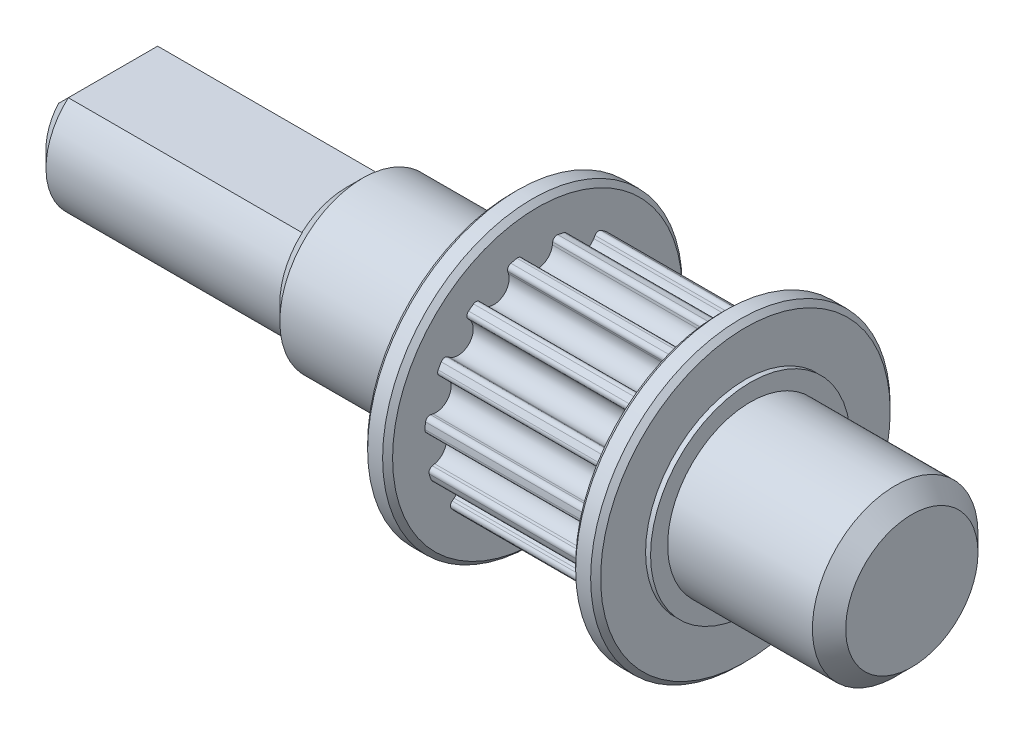
SolidWorks part; units mm, degrees
ref_plane "前视基准面" through (0, 0, 0) normal (0, 0, 1) x (1, 0, 0)
ref_plane "上视基准面" through (0, 0, 0) normal (0, 1, 0) x (1, 0, 0)
ref_plane "右视基准面" through (0, 0, 0) normal (1, 0, 0) x (0, 0, -1)
sketch "草图1" plane through (0, 0, 0) normal (0, 0, 1) x (1, 0, 0)
  line L0 (0, 0) -> (64.8368, 0) construction
  line L1 (0, 1.3558) -> (0, 6.779)
  line L2 (0, 6.779) -> (11, 6.779)
  line L3 (11, 6.779) -> (11, 2.7116)
  line L4 (11, 2.7116) -> (20, 2.7116)
  line L5 (20, 2.7116) -> (20, 1.3558)
  line L6 (20, 1.3558) -> (0, 1.3558)
  dimension "L" = 20
  dimension "B" = 11
  dimension "d" = 2.7116
  dimension "d1" = 5.4232
  dimension "da" = 13.558
revolve "旋转1" add sketch "草图1" angle 360 about L0
chamfer "倒角1" distance 1 angle 45 2 edges at (20, 0, 1.3558) (0, 0, 1.3558)
sketch "草图4" plane through (0, 0, 0) normal (-1, 0, 0) x (0, 0, 1)
  line L1 (-1, 0.9155) -> (1, 0.9155)
  line L2 (-1, 0.9155) -> (-1, 2.3558)
  line L3 (-1, 2.3558) -> (1, 2.3558)
  line L4 (1, 0.9155) -> (1, 2.3558)
  circle A0 centre (0, 0) radius 1.3558 construction
  point P6 (0, 2.3558)
  dimension "键槽高度" = 2.3558
  dimension "键槽宽度" = 2
  dimension "t1" = 1
extrude "切除-拉伸1" cut sketch "草图4" against normal through all
sketch "草图6" plane through (0, 0, 0) normal (1, 0, 0) x (0, 0, -1)
  line L0 (0, 0) -> (0, 30.6512) construction
  line L1 (0.921, 6.4432) -> (0.9032, 6.2981)
  line L2 (1.4809, 6.6153) -> (1.6775, 8.2168)
  line L3 (-1.4809, 6.6153) -> (-1.6775, 8.2168)
  line L4 (-0.921, 6.4432) -> (-0.9032, 6.2981)
  circle A0 centre (0, 0) radius 6.779 construction
  circle A1 centre (0, 0) radius 5.499 construction
  arc A2 (-0.9032, 6.2981) -> (0.9032, 6.2981) centre (0, 6.409) ccw
  arc A3 (1.6775, 8.2168) -> (-1.6775, 8.2168) centre (0, 0) ccw
  arc A4 (0.921, 6.4432) -> (1.2261, 6.6672) centre (1.1791, 6.4115) cw
  arc A5 (1.2261, 6.6672) -> (1.4809, 6.6153) centre (0, 0) cw
  arc A6 (-1.2261, 6.6672) -> (-1.4809, 6.6153) centre (0, 0) ccw
  arc A7 (-0.921, 6.4432) -> (-1.2261, 6.6672) centre (-1.1791, 6.4115) ccw
  point P7 (0, 1.9)
  point P8 (0, 29.3712)
  point P15 (0.954, 6.7115)
  dimension "D1" = 10.998
  dimension "ra" = 0.26
  dimension "rf" = 0.91
  dimension "hg" = 1.28
  dimension "D3" = 0.26
  dimension "D4" = 1.6136
  dimension "angle" = 14
  dimension "bw" = 1.9
extrude "切除-拉伸2" cut sketch "草图6" along normal up to next
ref_axis "基准轴1" through (-28.95, 0, 0) along (1, 0, 0)
pattern_circular "阵列(圆周)3" count 15 over 360 about axis through (-28.95, 0, 0) along (1, 0, 0) of "切除-拉伸2"
sketch "草图7" plane through (0, 0, 0) normal (-1, 0, 0) x (0, 0, 1)
  circle A0 centre (0, 0) radius 3
  dimension "D1" = 6
extrude "切除-拉伸3" cut sketch "草图7" against normal through all
sketch "草图9" plane through (0, 0, 0) normal (-1, 0, 0) x (0, 0, 1)
  circle A0 centre (0, 0) radius 9
  circle A1 centre (0, 0) radius 3 construction
  circle A2 centre (0, 0) radius 3
  dimension "D1" = 18
extrude "凸台-拉伸1" add sketch "草图9" along normal blind 1.5
sketch "草图10" plane through (11, 0, 0) normal (1, 0, 0) x (0, 0, -1)
  circle A0 centre (0, 0) radius 9
  circle A1 centre (0, 0) radius 9 construction
  circle A2 centre (0, 0) radius 3 construction
  circle A3 centre (0, 0) radius 3
extrude "凸台-拉伸2" add sketch "草图10" along normal blind 1.5
chamfer "倒角2" distance 0.3 angle 45 4 edges at (12.5, 0, -9) (11, 0, -9) (0, 0, 9) (-1.5, 0, 9)
sketch "草图15" plane through (-1.5, 0, 0) normal (-1, 0, 0) x (0, 0, 1)
  circle A0 centre (0, 0) radius 3
extrude "凸台-拉伸3" add sketch "草图15" against normal up to surface (14 mm away) up to face at (12.5, 0, -8.7)
sketch "草图16" plane through (-1.5, 0, 0) normal (-1, 0, 0) x (0, 0, 1)
  circle A0 centre (0, 0) radius 4.975
  dimension "D1" = 9.95
extrude "凸台-拉伸4" add sketch "草图16" along normal blind 10
sketch "草图17" plane through (-1.5, 0, 0) normal (-1, 0, 0) x (0, 0, 1)
  circle A0 centre (0, 0) radius 6
  dimension "D1" = 12
extrude "凸台-拉伸5" add sketch "草图17" along normal blind 0.3
ref_plane "基准面1" through (5.5, 0, 0) normal (1, 0, 0) x (0, 0, -1)
mirror "镜向2" about plane through (5.5, 0, 0) normal (1, 0, 0) of "凸台-拉伸5", "凸台-拉伸4"
sketch "草图18" plane through (-11.5, 0, 0) normal (-1, 0, 0) x (0, 0, 1)
  line L0 (-2.6834, 3) -> (2.6834, 3)
  arc A0 (-2.6834, 3) -> (2.6834, 3) centre (0, 0) ccw
  dimension "D1" = 8.05
  dimension "D2" = 3
extrude "凸台-拉伸6" add sketch "草图18" along normal blind 15
chamfer "倒角3" distance 1 angle 45 4 edges at (-26.5, 3, 0) (-26.5, -4.025, 0) (22.5, 0, 4.975) (-11.5, 0, 4.975)
equation "\"键槽高度@草图4\" = \"d@草图1\" / 2  + \"t1@草图4\""
equation "\"D1@草图6\" = \"da@草图1\"  - \"hg@草图6\" - \"hg@草图6\""
equation "\"D3@草图6\" = \"ra@草图6\""
